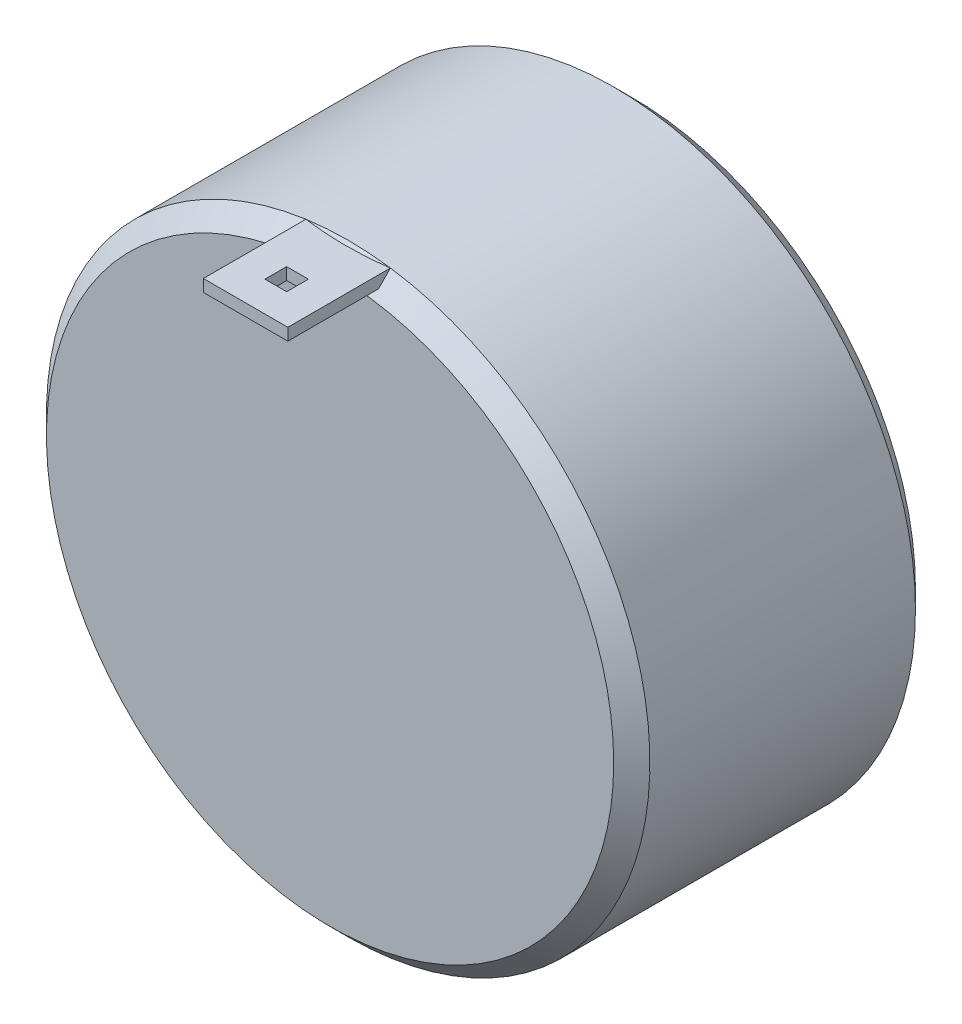
SolidWorks part; units mm, degrees
ref_plane "Front" through (0, 0, 0) normal (0, 0, 1) x (1, 0, 0)
ref_plane "Top" through (0, 0, 0) normal (0, 1, 0) x (1, 0, 0)
ref_plane "Right" through (0, 0, 0) normal (1, 0, 0) x (0, 0, -1)
sketch "Sketch1" plane through (0, 0, 0) normal (0, 0, 1) x (1, 0, 0)
  line L1 (0, 0) -> (50, 0) construction
  line L2 (0, 0) -> (0, 50) construction
  line L3 (0, 50) -> (50, 50) construction
  line L4 (50, 0) -> (50, 50) construction
  circle A0 centre (25, 25) radius 25
  dimension "D1" = 50
extrude "Boss-Extrude1" add sketch "Sketch1" along normal blind 25
chamfer "Chamfer1" distance 1.5 angle 45 2 edges at (50, 25, 0) (50, 25, 25)
sketch "Sketch2" plane through (0, 0, 25) normal (0, 0, 1) x (1, 0, 0)
  line L1 (21.5, 49.7538) -> (28.5, 49.7538)
  line L2 (21.5, 49.7538) -> (21.5, 48.7538)
  line L3 (21.5, 48.7538) -> (28.5, 48.7538)
  line L4 (28.5, 49.7538) -> (28.5, 48.7538)
  circle A0 centre (25, 25) radius 25 construction
  dimension "D1" = 7
  dimension "D2" = 1
extrude "Boss-Extrude2" add sketch "Sketch2" along normal blind 7 and the other way blind 7
sketch "Sketch3" plane through (0, 49.7538, 0) normal (0, 1, 0) x (1, 0, 0)
  line L0 (28.5, -32) -> (21.5, -32) construction
  line L1 (25.9, -29.5) -> (24.1, -29.5)
  line L2 (25.9, -29.5) -> (25.9, -27.7)
  line L3 (25.9, -27.7) -> (24.1, -27.7)
  line L4 (24.1, -29.5) -> (24.1, -27.7)
  line L5 (25, -32) -> (25, -29.5) construction
  dimension "D1" = 1.8
  dimension "D2" = 2.5
extrude "Cut-Extrude1" cut sketch "Sketch3" against normal blind 7
